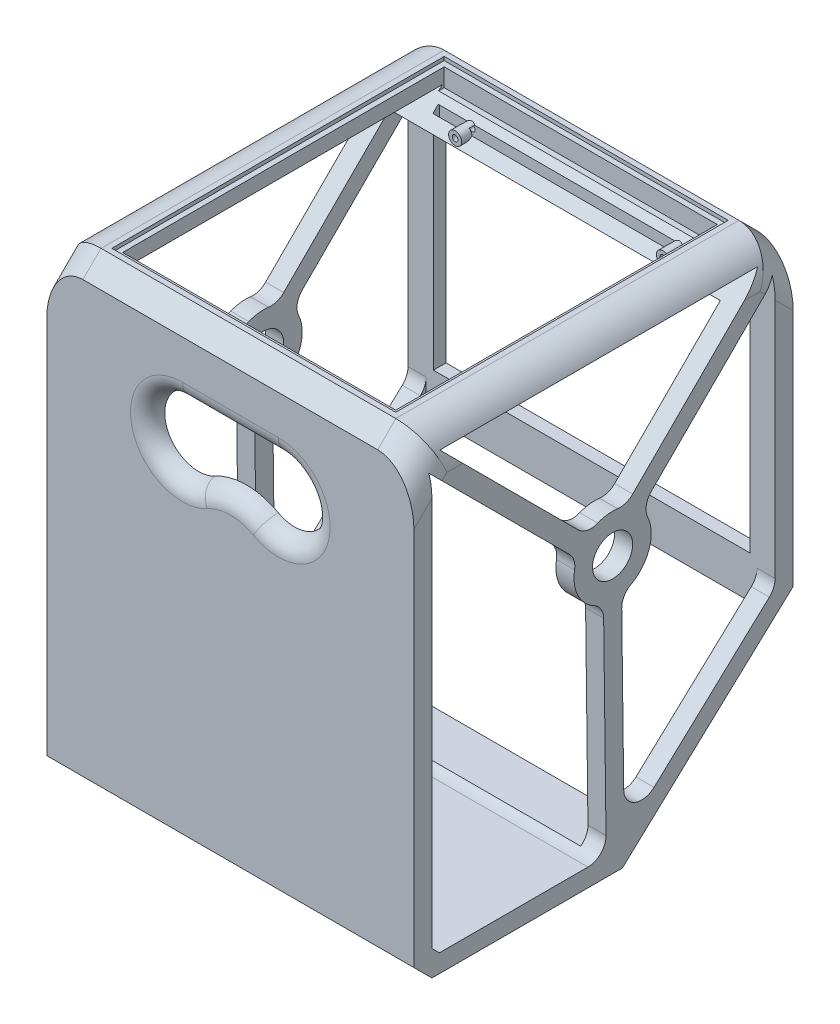
SolidWorks part; units mm, degrees
ref_plane "Front Plane" through (0, 0, 0) normal (0, 0, 1) x (1, 0, 0)
ref_plane "Top Plane" through (0, 0, 0) normal (0, 1, 0) x (1, 0, 0)
ref_plane "Right Plane" through (0, 0, 0) normal (1, 0, 0) x (0, 0, -1)
sketch "Profile" plane through (0, 0, 0) normal (1, 0, 0) x (0, 0, -1)
  line L0 (0, 248.2327) -> (10, 258.2327)
  line L1 (10, 0) -> (115.4308, 0)
  line L2 (0, 10) -> (0, 248.2327)
  line L3 (10, 258.2327) -> (200, 258.2327)
  line L4 (210, 87.8057) -> (210, 248.2327)
  line L5 (200, 258.2327) -> (210, 248.2327)
  line L6 (0, 10) -> (10, 0)
  line L7 (115.4308, 0) -> (210, 87.8057)
  line L9 (17.0711, 248.2327) -> (192.9289, 248.2327)
  line L11 (200, 92.1667) -> (200, 241.1617)
  line L12 (116.4476, 14.5898) -> (200, 92.1667)
  line L13 (14.1421, 10) -> (106.5038, 10)
  line L14 (10, 14.1421) -> (14.1421, 10)
  line L15 (10, 14.1421) -> (10, 241.1617)
  line L18 (116.4476, 14.5898) -> (114.9996, 131.0792)
  line L19 (106.5038, 10) -> (105.0004, 130.9549)
  line L20 (105.0004, 130.9549) -> (105.0004, 131.6097)
  line L22 (114.9996, 131.0792) -> (114.9996, 131.6097)
  line L26 (111.5042, 10) -> (200, 92.1667) construction
  line L27 (14.1421, 10) -> (111.5042, 10) construction
  line L30 (10, 241.1617) -> (89.4051, 161.7566)
  line L31 (17.0711, 248.2327) -> (96.4017, 168.9021)
  line L32 (14.1421, 248.2327) -> (195.8579, 248.2327) construction
  line L33 (192.9289, 248.2327) -> (118.3842, 173.688)
  line L34 (200, 241.1617) -> (125.7265, 166.8882)
  line L35 (118.3842, 173.688) -> (117.2225, 172.5263)
  line L36 (89.4051, 161.7566) -> (90.3437, 160.8179)
  line L37 (200, 92.1667) -> (200, 244.0906) construction
  line L38 (10, 14.1421) -> (10, 244.0906) construction
  line L40 (195.8579, 248.2327) -> (200, 244.0906) construction
  line L41 (10, 244.0906) -> (14.1421, 248.2327) construction
  circle A0 centre (110, 152.4) radius 11.1125
  arc A1 (114.9996, 131.6097) -> (125.7265, 166.8882) centre (110, 152.4) ccw
  arc A2 (90.3437, 160.8179) -> (105.0004, 131.6097) centre (110, 152.4) ccw
  arc A3 (117.2225, 172.5263) -> (96.4017, 168.9021) centre (110, 152.4) ccw
  point P0 (0, 0)
  point P1 (210, 258.2327)
  point P2 (0, 258.2327)
  point P3 (200.5236, 84.6121)
  dimension "D1" = 120
  dimension "D10" = 22.225
  dimension "D8" = 10
  dimension "D3" = 10
  dimension "D2" = 10
  dimension "D6" = 110
  dimension "D7" = 190
  dimension "D9" = 152.4
  dimension "D11" = 10
extrude "Boss-Extrude1" add sketch "Profile" along normal blind 203.2
sketch "Eyeport" plane through (0, 0, 0) normal (0, 0, 1) x (1, 0, 0)
  line L0 (75, 216.5909) -> (128.2, 216.5909)
  line L1 (0, 248.2327) -> (0, 10) construction
  line L2 (203.2, 248.2327) -> (203.2, 10) construction
  arc A0 (75, 216.5909) -> (84.0286, 181.6109) centre (75, 197.9357) ccw
  arc A1 (119.1714, 181.6109) -> (128.2, 216.5909) centre (128.2, 197.9357) ccw
  arc A2 (119.1714, 181.6109) -> (84.0286, 181.6109) centre (101.6, 149.8394) ccw
  dimension "D1" = 75
  dimension "D2" = 75
extrude "Cut-Extrude - Eyeport" cut sketch "Eyeport" against normal blind 10
fillet "Fillet1" radius 20 6 edges at (203.2, 253.2327, -205) (0, 253.2327, -205) (0, 253.2327, -5) (203.2, 253.2327, -5) (203.2, 258.2327, -105) (0, 258.2327, -105)
fillet "Fillet2" radius 10 6 edges at (101.6, 131.6097, -105.0004) (101.6, 131.6097, -114.9996) (101.6, 166.8882, -125.7265) (101.6, 160.8179, -90.3437) (101.6, 168.9021, -96.4017) (101.6, 172.5263, -117.2225)
fillet "Fillet3" radius 10 4 edges at (101.6, 216.5909, 0) (146.2632, 193.2735, 0) (101.6, 186.1462, 0) (56.9368, 193.2735, 0)
sketch "Interior" plane through (0, 0, -200) normal (0, 0, 1) x (1, 0, 0)
  line L0 (0, 87.8057) -> (0, 219.9485) construction
  line L1 (10, 234.9727) -> (193.2, 234.9727)
  line L2 (10, 234.9727) -> (10, 12)
  line L3 (10, 12) -> (193.2, 12)
  line L4 (193.2, 234.9727) -> (193.2, 12)
  line L5 (203.2, 87.8057) -> (203.2, 219.9485) construction
  line L6 (203.2, 0) -> (0, 0) construction
  dimension "D1" = 10
  dimension "D2" = 10
  dimension "D3" = 12
extrude "Cut-Extrude2" cut sketch "Interior" along normal blind 191
sketch "DisplayMount" plane through (0, 0, -179.012) normal (0, 0, -1) x (-1, 0, 0)
  circle A0 centre (-162.044, 240.0279) radius 1.6
  circle A1 centre (-47.044, 240.0279) radius 1.6
  circle A2 centre (-162.044, 240.0279) radius 3.6
  circle A3 centre (-47.044, 240.0279) radius 3.6
  dimension "D1" = 115
  dimension "D2" = 2
extrude "Boss-Extrude2" add sketch "DisplayMount" along normal blind 16
sketch "Sketch10" plane through (0, 0, -179.012) normal (0, 0, -1) x (-1, 0, 0)
  circle A0 centre (-162.044, 240.0279) radius 1.6
  circle A1 centre (-47.044, 240.0279) radius 1.6
extrude "Cut-Extrude3" cut sketch "Sketch10" along normal blind 19
sketch "Sketch11" plane through (0, 234.9727, 0) normal (0, -1, 0) x (1, 0, 0)
  line L0 (10, -128.3552) -> (10, -200) construction
  line L1 (29, -184.7241) -> (174.2, -184.7241)
  line L2 (29, -184.7241) -> (29, -188.512)
  line L3 (29, -188.512) -> (174.2, -188.512)
  line L4 (174.2, -184.7241) -> (174.2, -188.512)
  line L5 (193.2, -200) -> (193.2, -128.3552) construction
  point P4 (29, -186.618)
  dimension "D1" = 19
  dimension "D2" = 19
extrude "Cut-Extrude4" cut sketch "Sketch11" against normal blind 8
sketch "Bolthole" plane through (0, 0, -198.012) normal (0, 0, 1) x (1, 0, 0)
  line L5 (134.1531, 236.1619) -> (166.9191, 236.1619) construction
  line L6 (43.194, 243.8939) -> (50.894, 243.8939)
  line L13 (43.194, 243.8939) -> (43.194, 236.1619)
  line L14 (43.194, 236.1619) -> (50.894, 236.1619)
  line L15 (50.894, 243.8939) -> (50.894, 236.1619)
  line L16 (43.194, 243.8939) -> (50.894, 236.1619) construction
  line L17 (43.194, 236.1619) -> (50.894, 243.8939) construction
  line L18 (158.194, 243.8939) -> (165.894, 243.8939)
  line L19 (158.194, 243.8939) -> (158.194, 236.1619)
  line L20 (158.194, 236.1619) -> (165.894, 236.1619)
  line L21 (165.894, 243.8939) -> (165.894, 236.1619)
  line L22 (158.194, 243.8939) -> (165.894, 236.1619) construction
  line L23 (158.194, 236.1619) -> (165.894, 243.8939) construction
  line L24 (165.894, 159.6279) -> (165.894, 237.4279) construction
  point P0 (47.044, 240.0279)
  point P6 (162.044, 240.0279)
extrude "Cut-Extrude5" cut sketch "Bolthole" along normal blind 4
sketch "Sketch14" plane through (0, 0, -210) normal (0, 0, -1) x (-1, 0, 0)
  line L5 (-203.2, 87.8057) -> (0, 87.8057) construction
  line L6 (-193.2, 219.9485) -> (-182.4131, 233.6219)
  line L7 (-182.4131, 233.6219) -> (-20.7869, 233.6219)
  line L8 (-20.7869, 233.6219) -> (-10, 219.9485)
  line L13 (-193.2, 219.9485) -> (-193.2, 97.8057)
  line L14 (-193.2, 97.8057) -> (-10, 97.8057)
  line L15 (-10, 97.8057) -> (-10, 219.9485)
  dimension "D1" = 10
  dimension "D2" = 10
  dimension "D3" = 10
extrude "Cut-Extrude6" cut sketch "Sketch14" against normal blind 3
sketch "Sketch16" plane through (0, 0, -207) normal (0, 0, -1) x (-1, 0, 0)
  line L8 (-189.2, 218.5606) -> (-189.2, 101.8057)
  line L9 (-189.2, 101.8057) -> (-14, 101.8057)
  line L10 (-14, 101.8057) -> (-14, 218.5606)
  line L11 (-22.7262, 229.6219) -> (-180.4738, 229.6219)
  line L12 (-189.2, 218.5606) -> (-189.2, 101.8057)
  line L13 (-189.2, 101.8057) -> (-14, 101.8057)
  line L14 (-14, 101.8057) -> (-14, 218.5606)
  line L18 (-22.7262, 229.6219) -> (-180.4738, 229.6219)
  line L19 (-180.4738, 229.6219) -> (-189.2, 218.5606)
  line L20 (-180.4738, 229.6219) -> (-189.2, 218.5606)
  line L21 (-14, 218.5606) -> (-22.7262, 229.6219)
  line L22 (-14, 218.5606) -> (-22.7262, 229.6219)
  dimension "D1" = 4
extrude "Cut-Extrude7" cut sketch "Sketch16" against normal blind 7
sketch "Sketch19" plane through (0, 258.2327, 0) normal (0, 1, 0) x (1, 0, 0)
  line L8 (23, 13) -> (180.2, 13)
  line L9 (180.2, 13) -> (180.2, 197)
  line L10 (180.2, 197) -> (23, 197)
  line L11 (23, 197) -> (23, 13)
  line L12 (23, 13) -> (180.2, 13)
  line L13 (180.2, 13) -> (180.2, 197)
  line L14 (180.2, 197) -> (23, 197)
  line L15 (23, 197) -> (23, 13)
  dimension "D1" = 3
extrude "Cut-Extrude10" cut sketch "Sketch19" against normal blind 2
sketch "Sketch20" plane through (0, 256.2327, 0) normal (0, 1, 0) x (1, 0, 0)
  line L8 (26, 194) -> (26, 16)
  line L9 (26, 16) -> (177.2, 16)
  line L10 (177.2, 16) -> (177.2, 194)
  line L11 (177.2, 194) -> (26, 194)
  line L12 (26, 194) -> (26, 16)
  line L13 (26, 16) -> (177.2, 16)
  line L14 (177.2, 16) -> (177.2, 194)
  line L15 (177.2, 194) -> (26, 194)
  dimension "D1" = 3
extrude "Cut-Extrude11" cut sketch "Sketch20" against normal blind 10
fillet "Fillet4" radius 10 5 edges at (101.6, 10, -106.5038) (5, 14.5898, -116.4476) (198.2, 14.5898, -116.4476) (5, 92.1667, -200) (198.2, 92.1667, -200)
